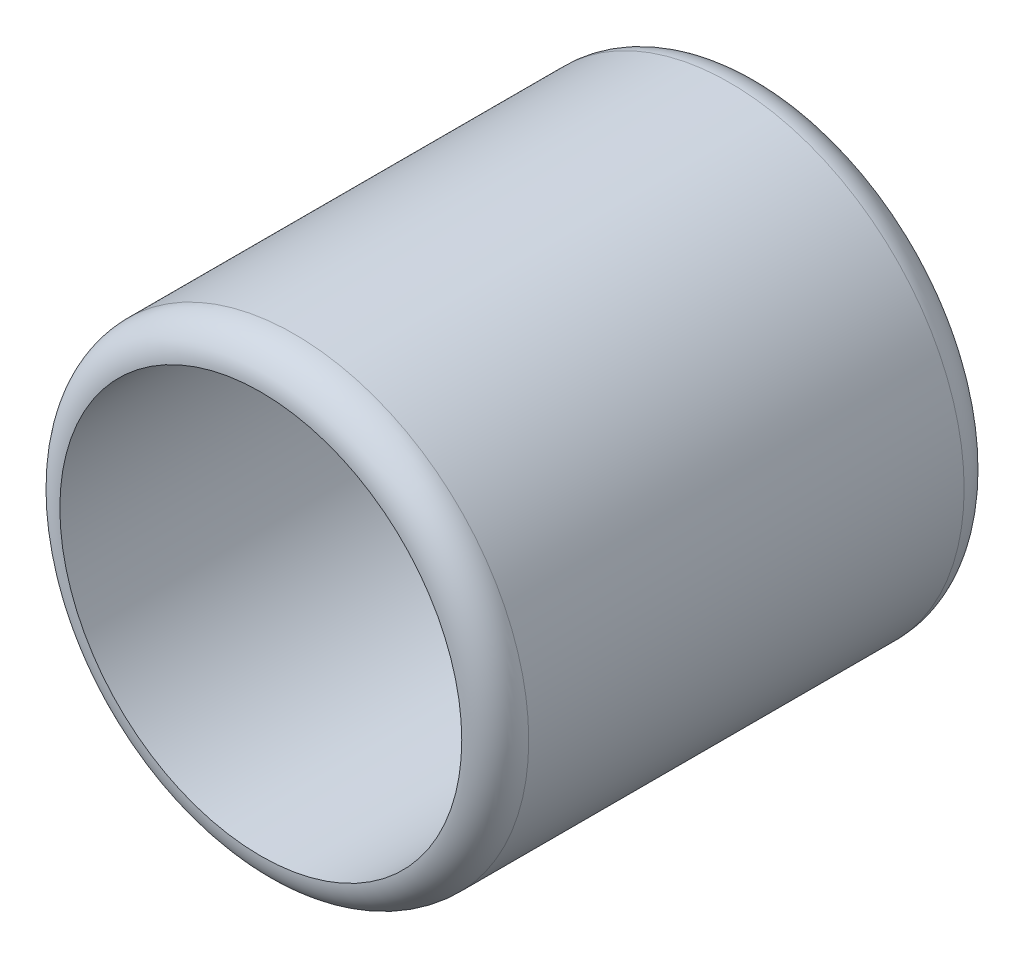
SolidWorks part; units mm, degrees
material "BUTYL"
ref_plane "Front Plane" through (0, 0, 0) normal (0, 0, 1) x (1, 0, 0)
ref_plane "Top Plane" through (0, 0, 0) normal (0, 1, 0) x (1, 0, 0)
ref_plane "Right Plane" through (0, 0, 0) normal (1, 0, 0) x (0, 0, -1)
sketch "Sketch1" plane through (0, 0, 0) normal (0, 0, 1) x (1, 0, 0)
  circle A0 centre (0, 0) radius 6
  circle A1 centre (0, 0) radius 7
  dimension "D1" = 12
  dimension "D2" = 14
extrude "Boss-Extrude1" add sketch "Sketch1" along normal mid plane 15
fillet "Fillet1" radius 1 2 edges at (7, 0, -7.5) (7, 0, 7.5)
